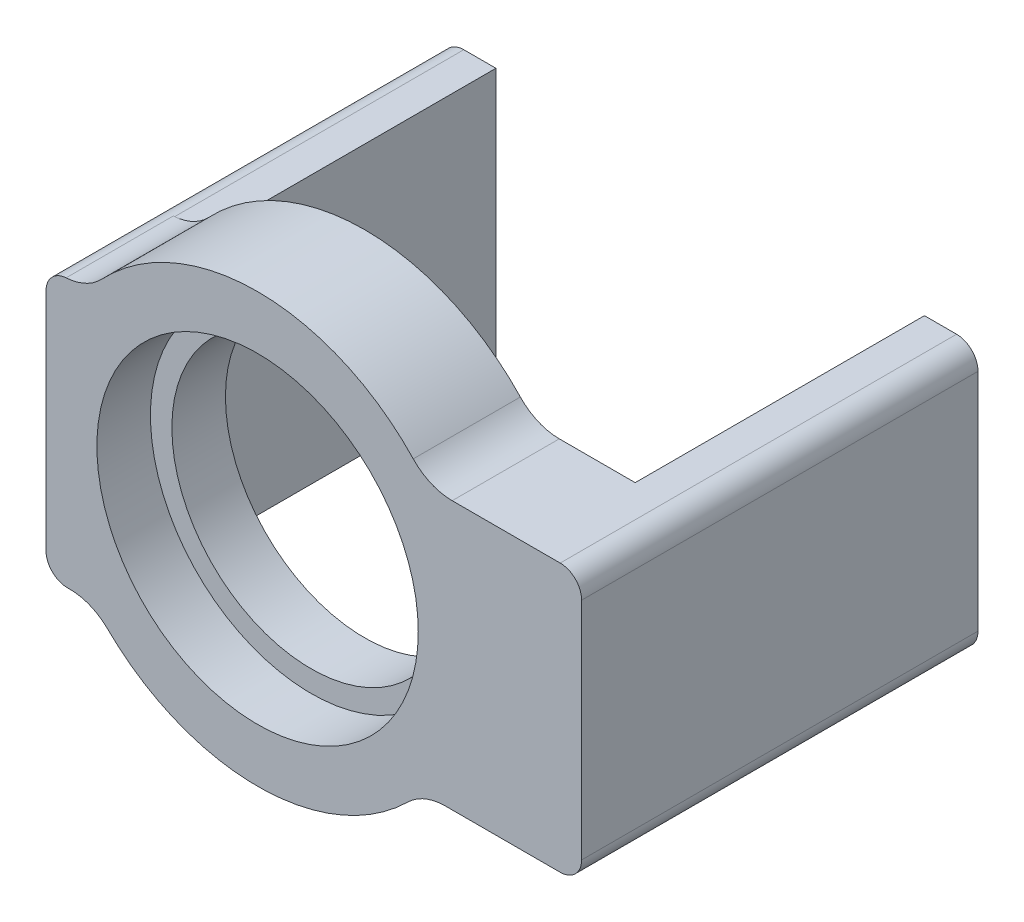
SolidWorks part; units mm, degrees
ref_plane "Front Plane" through (0, 0, 0) normal (0, 0, 1) x (1, 0, 0)
ref_plane "Top Plane" through (0, 0, 0) normal (0, 1, 0) x (1, 0, 0)
ref_plane "Right Plane" through (0, 0, 0) normal (1, 0, 0) x (0, 0, -1)
sketch "Sketch2" plane through (0, 0, 1.8) normal (0, 0, 1) x (1, 0, 0)
  line L5 (-76.5966, -98.699) -> (-81, -98.699)
  line L6 (-77.1172, -73.699) -> (-81, -73.699)
  line L9 (-31, -73.699) -> (-45.3828, -73.699)
  line L10 (-31, -98.699) -> (-45.9034, -98.699)
  line L14 (-31, -73.699) -> (-31, -98.699)
  line L16 (-81, -98.699) -> (-81, -73.699)
  circle A1 centre (-61.25, -85.874) radius 15
  arc A2 (-76.5966, -98.699) -> (-45.9034, -98.699) centre (-61.25, -85.874) ccw
  arc A4 (-45.3828, -73.699) -> (-77.1172, -73.699) centre (-61.25, -85.874) ccw
  point P6 (0, 0)
  point P8 (0, 0)
  point P9 (0, 0)
  point P15 (0, 0)
  point P17 (0, 0)
  point P19 (0, 0)
  point P21 (0, 0)
  point P22 (0, 0)
  point P23 (0, 0)
  point P24 (0, 0)
  point P25 (0, 0)
extrude "Boss-Extrude1" add sketch "Sketch2" against normal blind 5
sketch "Sketch3" plane through (0, 0, -3.2) normal (0, 0, -1) x (-1, 0, 0)
  line L3 (76.5966, -98.699) -> (81, -98.699)
  line L4 (76.5966, -98.699) -> (81, -98.699)
  line L5 (31, -73.699) -> (31, -98.699)
  line L14 (81, -73.699) -> (77.1172, -73.699)
  line L15 (81, -73.699) -> (77.1172, -73.699)
  line L16 (45.3828, -73.699) -> (31, -73.699)
  line L17 (45.3828, -73.699) -> (31, -73.699)
  line L18 (31, -73.699) -> (31, -98.699)
  line L20 (31, -98.699) -> (45.9034, -98.699)
  line L21 (31, -98.699) -> (45.9034, -98.699)
  line L22 (81, -98.699) -> (81, -73.699)
  line L23 (81, -98.699) -> (81, -73.699)
  arc A1 (45.9034, -98.699) -> (76.5966, -98.699) centre (61.25, -85.874) ccw
  arc A2 (45.9034, -98.699) -> (76.5966, -98.699) centre (61.25, -85.874) ccw
  circle A3 centre (61.25, -85.874) radius 13
  arc A6 (77.1172, -73.699) -> (45.3828, -73.699) centre (61.25, -85.874) ccw
  arc A8 (77.1172, -73.699) -> (45.3828, -73.699) centre (61.25, -85.874) ccw
  dimension "D1" = 0
extrude "Boss-Extrude2" add sketch "Sketch3" along normal blind 5
sketch "Sketch6" plane through (0, 0, -8.2) normal (0, 0, -1) x (-1, 0, 0)
  line L0 (81, -73.699) -> (77.1172, -73.699) construction
  line L1 (31, -98.699) -> (36, -98.699)
  line L2 (31, -98.699) -> (31, -73.699)
  line L3 (31, -73.699) -> (36, -73.699)
  line L4 (36, -98.699) -> (36, -73.699)
  line L5 (81, -98.699) -> (76, -98.699)
  line L6 (81, -98.699) -> (81, -73.699)
  line L7 (81, -73.699) -> (76, -73.699)
  line L8 (76, -98.699) -> (76, -73.699)
  line L9 (45.3828, -73.699) -> (31, -73.699) construction
  point P10 (0, 0)
  point P13 (0, 0)
  point P14 (0, 0)
extrude "Boss-Extrude3" add sketch "Sketch6" along normal up to surface (27 mm away)
fillet "Fillet1" radius 2 4 edges at (-31, -73.699, -16.7) (-31, -98.699, -16.7) (-81, -73.699, -16.7) (-81, -98.699, -16.7)
fillet "Fillet2" radius 5 4 edges at (-45.3828, -73.699, -3.2) (-45.9034, -98.699, -3.2) (-77.1172, -73.699, -3.2) (-76.5966, -98.699, -3.2)
